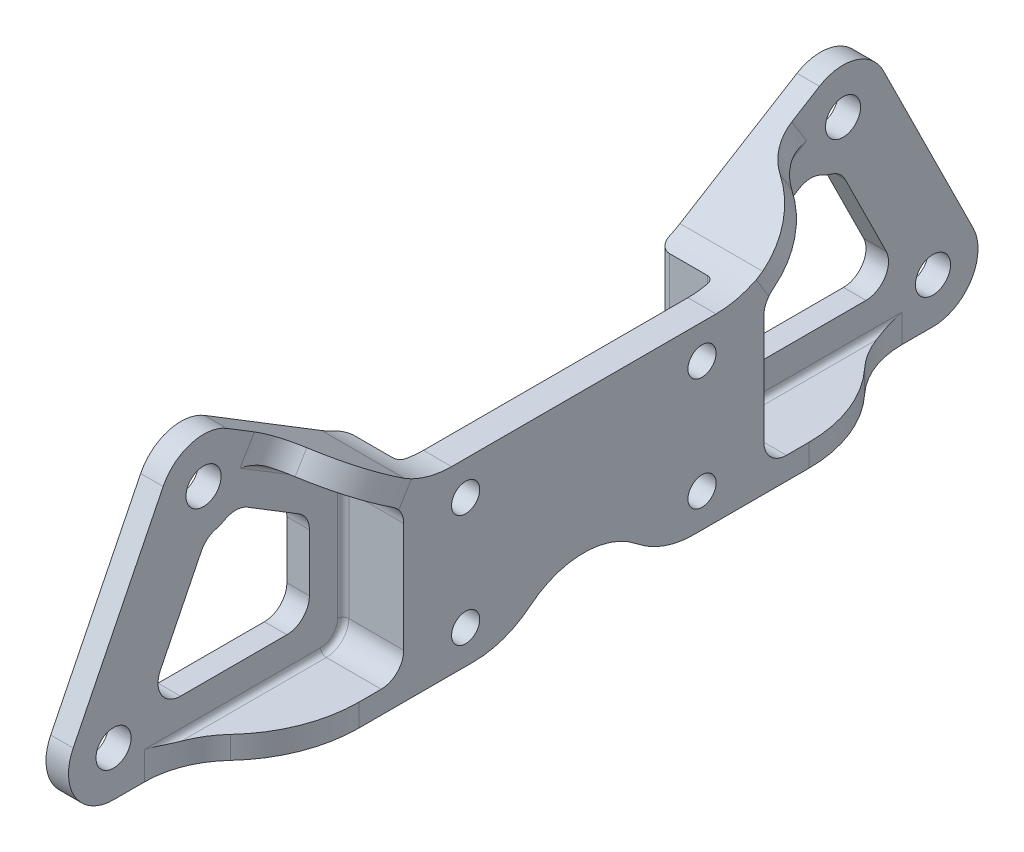
SolidWorks part; units mm, degrees
material "6061-T6 (SS)"
ref_plane "Front Plane" through (0, 0, 0) normal (0, 0, 1) x (1, 0, 0)
ref_plane "Top Plane" through (0, 0, 0) normal (0, 1, 0) x (1, 0, 0)
ref_plane "Right Plane" through (0, 0, 0) normal (1, 0, 0) x (0, 0, -1)
sketch "UprightGeometry" plane through (0, 0, 0) normal (1, 0, 0) x (0, 0, -1)
  line L0 (0, 85.725) -> (0, 0) construction
  line L1 (-44.45, -31.75) -> (44.45, -31.75)
  line L2 (-44.45, -31.75) -> (-44.45, 132.0361)
  line L3 (-44.45, 132.0361) -> (44.45, 132.0361)
  line L4 (44.45, -31.75) -> (44.45, 132.0361)
  line L5 (-22.225, 107.95) -> (22.225, 107.95)
  line L6 (-22.225, 107.95) -> (-22.225, 63.5)
  line L7 (-22.225, 63.5) -> (22.225, 63.5)
  line L8 (22.225, 107.95) -> (22.225, 63.5)
  line L9 (-22.225, 107.95) -> (22.225, 63.5) construction
  line L10 (-22.225, 63.5) -> (22.225, 107.95) construction
  line L11 (-44.45, 38.1) -> (44.45, 38.1) construction
  line L12 (-84.8616, 85.725) -> (88.724, 85.725) construction
  line L13 (88.724, 79.375) -> (-84.8616, 79.375) construction
  line L14 (88.724, 74.7268) -> (-142.7243, 74.7268) construction
  circle A0 centre (0, 0) radius 12.7
  circle A1 centre (0, 0) radius 19.05
  circle A2 centre (-33.3375, 53.975) radius 3.9688
  circle A3 centre (33.3375, 53.975) radius 3.9687
  circle A4 centre (33.3375, 22.225) radius 3.9687
  circle A5 centre (-33.3375, 22.225) radius 3.9688
  point P8 (0, 85.725)
  dimension "D6" = 25.4
  dimension "D7" = 38.1
  dimension "D9" = 7.9375
  dimension "D1" = 85.725
  dimension "D2" = 44.45
  dimension "D3" = 44.45
  dimension "D4" = 88.9
  dimension "D5" = 31.75
  dimension "D8" = 47.625
  dimension "D10" = 66.675
  dimension "D11" = 31.75
  dimension "D12" = 6.35
  dimension "D13" = 10.9982
sketch "CaliperGeometry" plane through (0, 0, 0) normal (1, 0, 0) x (0, 0, -1)
  line L0 (0, 0) -> (0, 136.5858) construction
  line L1 (0, 0) -> (-119.102, 59.0447) construction
  line L2 (-90.1858, 76.6033) -> (-115.5698, 25.4) construction
  line L3 (0, 0) -> (119.102, 59.0447) construction
  line L4 (90.1858, 76.6033) -> (115.5698, 25.4) construction
  line L5 (-44.45, 12.7) -> (-150.9464, 12.7) construction
  line L7 (-44.45, -31.75) -> (-44.45, 132.0361) construction
  line L8 (-22.225, 63.5) -> (22.225, 63.5) construction
  line L9 (-44.45, 63.5) -> (-66.5242, 77.0108) construction
  circle A0 centre (0, 0) radius 110 construction
  circle A1 centre (-115.5698, 25.4) radius 4.953
  circle A2 centre (-90.1858, 76.6033) radius 4.953
  circle A3 centre (115.5698, 25.4) radius 4.953
  circle A4 centre (90.1858, 76.6033) radius 4.953
  circle A5 centre (-115.5698, 25.4) radius 12.7 construction
  circle A6 centre (-90.1858, 76.6033) radius 12.7 construction
  point P7 (-102.8778, 51.0016)
  point P10 (-98.554, 48.8581)
  dimension "D1" = 220
  dimension "D3" = 9.906
  dimension "D7" = 25.4
  dimension "D2" = 57.15
  dimension "D4" = 4.826
  dimension "D5" = 63.63
  dimension "D6" = 50.8
sketch "Sketch3" plane through (0, 0, 0) normal (1, 0, 0) x (0, 0, -1)
  line L0 (-44.45, 63.5) -> (44.45, 63.5)
  line L1 (-44.45, -31.75) -> (-44.45, 132.0361) construction
  line L2 (0, 85.725) -> (0, 0) construction
  line L3 (-44.45, 12.7) -> (44.45, 12.7)
  line L4 (-44.45, 12.7) -> (-115.5698, 12.7)
  line L5 (-44.45, 63.5) -> (-83.5559, 87.4353)
  line L6 (-126.9483, 31.0409) -> (-101.5643, 82.2442)
  line L7 (126.9483, 31.0409) -> (101.5643, 82.2442)
  line L8 (44.45, 63.5) -> (83.5559, 87.4353)
  line L9 (0, 0) -> (-119.102, 59.0447) construction
  line L10 (-22.225, 63.5) -> (22.225, 63.5) construction
  line L11 (0, 0) -> (0, 85.725) construction
  line L12 (44.45, 12.7) -> (115.5698, 12.7)
  circle A0 centre (-90.1858, 76.6033) radius 4.953 construction
  circle A1 centre (-115.5698, 25.4) radius 4.953 construction
  circle A4 centre (33.3375, 53.975) radius 3.9688 construction
  circle A5 centre (-33.3375, 53.975) radius 3.9688 construction
  circle A6 centre (-33.3375, 22.225) radius 3.9688 construction
  circle A7 centre (33.3375, 22.225) radius 3.9688 construction
  circle A8 centre (-90.1858, 76.6033) radius 4.953
  circle A9 centre (-115.5698, 25.4) radius 4.953
  arc A10 (83.5559, 87.4353) -> (101.5643, 82.2442) centre (90.1858, 76.6033) cw
  arc A11 (115.5698, 12.7) -> (126.9483, 31.0409) centre (115.5698, 25.4) ccw
  circle A12 centre (33.3375, 53.975) radius 3.9688
  circle A13 centre (-33.3375, 53.975) radius 3.9688
  circle A14 centre (-33.3375, 22.225) radius 3.9688
  circle A15 centre (33.3375, 22.225) radius 3.9687
  arc A16 (-115.5698, 12.7) -> (-126.9483, 31.0409) centre (-115.5698, 25.4) cw
  arc A17 (-83.5559, 87.4353) -> (-101.5643, 82.2442) centre (-90.1858, 76.6033) ccw
  circle A18 centre (115.5698, 25.4) radius 4.953
  circle A19 centre (90.1858, 76.6033) radius 4.953
  point P7 (0, 63.5)
  point P17 (-114.2563, 56.6425)
  point P29 (0, 12.7)
  point P34 (114.2563, 56.6425)
  dimension "D2" = 12.7
extrude "Boss-Extrude1" add sketch "Sketch3" along normal blind 7.9375
sketch "SpindleGeometry" plane through (0, 0, 0) normal (0, 0, 1) x (1, 0, 0)
  line L0 (0, -31.8425) -> (-38.1, -31.8425)
  line L1 (0, -31.75) -> (0, 132.0361) construction
  line L2 (0, -110) -> (0, 110) construction
  line L3 (-38.1, -31.8425) -> (-38.1, 132.0361)
  line L4 (-38.1, 132.0361) -> (0, 132.0361)
  line L5 (0, 0) -> (116.0127, 0) construction
  line L6 (0, 0) -> (0, 136.5858) construction
  line L7 (27.9, -110) -> (22.9, -110)
  line L8 (27.9, -110) -> (27.9, 110)
  line L9 (27.9, 110) -> (22.9, 110)
  line L10 (22.9, -110) -> (22.9, 110)
  line L11 (25.4, 0) -> (25.4, -129.8502) construction
  line L12 (0, -31.8425) -> (0, 132.0361) construction
  line L13 (-9.144, 104.2064) -> (-9.144, -104.3427) construction
  line L14 (-15.494, 104.2064) -> (-15.494, -104.3427) construction
  line L15 (9.525, 80.2257) -> (9.525, 91.2243)
  line L16 (9.525, 91.2243) -> (0, 96.7235)
  line L17 (0, 96.7235) -> (-9.525, 91.2243)
  line L18 (-9.525, 91.2243) -> (-9.525, 80.2257)
  line L19 (-9.525, 80.2257) -> (0, 74.7265)
  line L20 (0, 74.7265) -> (9.525, 80.2257)
  circle A0 centre (0, 85.725) radius 10.9985 construction
  point P11 (25.4, 0)
  point P16 (0, 110)
  dimension "D1" = 38.1
  dimension "D2" = 5
  dimension "D3" = 25.4
  dimension "D4" = 34.544
  dimension "D5" = 9.144
  dimension "D6" = 19.05
  dimension "D8" = 6.35
sketch "Sketch5" plane through (0, 0, 0) normal (1, 0, 0) x (0, 0, -1)
  line L0 (-44.45, 63.5) -> (-83.5559, 87.4353) construction
  line L1 (-101.5643, 82.2442) -> (-126.9483, 31.0409) construction
  line L3 (126.9483, 31.0409) -> (101.5643, 82.2442) construction
  line L4 (83.5559, 87.4353) -> (44.45, 63.5) construction
  line L5 (-115.5698, 12.7) -> (115.5698, 12.7) construction
  line L6 (-44.45, 63.5) -> (-83.5559, 87.4353)
  line L7 (-101.5643, 82.2442) -> (-126.9483, 31.0409)
  line L8 (-115.5698, 12.7) -> (-44.45, 12.7)
  line L9 (126.9483, 31.0409) -> (101.5643, 82.2442)
  line L10 (83.5559, 87.4353) -> (44.45, 63.5)
  line L11 (44.45, 12.7) -> (115.5698, 12.7)
  line L12 (-44.45, -31.75) -> (-44.45, 132.0361) construction
  line L13 (44.45, -31.75) -> (44.45, 132.0361) construction
  line L14 (-44.45, 12.7) -> (-44.45, 63.5)
  line L15 (44.45, 12.7) -> (44.45, 63.5)
  arc A0 (-83.5559, 87.4353) -> (-101.5643, 82.2442) centre (-90.1858, 76.6033) ccw construction
  arc A1 (-126.9483, 31.0409) -> (-115.5698, 12.7) centre (-115.5698, 25.4) ccw construction
  arc A2 (115.5698, 12.7) -> (126.9483, 31.0409) centre (115.5698, 25.4) ccw construction
  arc A3 (101.5643, 82.2442) -> (83.5559, 87.4353) centre (90.1858, 76.6033) ccw construction
  arc A4 (-83.5559, 87.4353) -> (-101.5643, 82.2442) centre (-90.1858, 76.6033) ccw
  arc A5 (-126.9483, 31.0409) -> (-115.5698, 12.7) centre (-115.5698, 25.4) ccw
  arc A6 (115.5698, 12.7) -> (126.9483, 31.0409) centre (115.5698, 25.4) ccw
  arc A7 (101.5643, 82.2442) -> (83.5559, 87.4353) centre (90.1858, 76.6033) ccw
  circle A8 centre (-90.1858, 76.6033) radius 4.953 construction
  circle A9 centre (-115.5698, 25.4) radius 4.953 construction
  circle A10 centre (115.5698, 25.4) radius 4.953 construction
  circle A11 centre (90.1858, 76.6033) radius 4.953 construction
  circle A12 centre (-90.1858, 76.6033) radius 4.953
  circle A13 centre (-115.5698, 25.4) radius 4.953
  circle A14 centre (115.5698, 25.4) radius 4.953
  circle A15 centre (90.1858, 76.6033) radius 4.953
extrude "Boss-Extrude2" add sketch "Sketch5" along direction (1, 0, 0) on the side against the normal up to vertex (15.494 mm away) up to point (-15.494, 104.2064, 0)
sketch "Sketch10" plane through (0, 0, 0) normal (1, 0, 0) x (0, 0, -1)
  circle A2 centre (0, 0) radius 23.8125
  circle A3 centre (0, 0) radius 23.8125
  dimension "D1" = 4.7625
extrude "Cut-Extrude3" cut sketch "Sketch10" along normal through all
sketch "Sketch7" plane through (7.9375, 0, 0) normal (-1, 0, 0) x (0, 0, 1)
  line L0 (81.9704, 71.7423) -> (79.9379, 85.2209)
  line L1 (0, 0) -> (119.102, 59.0447) construction
  line L2 (-0.0024, -0.0012) -> (-71.617, -35.5041) construction
  line L3 (106.7271, 21.8044) -> (115.5698, 12.7)
  line L5 (95.5306, 25.4836) -> (90.8737, 24.708)
  line L7 (44.45, 63.5) -> (83.5559, 87.4353) construction
  line L8 (101.5643, 82.2442) -> (126.9483, 31.0409) construction
  line L9 (44.45, 63.5) -> (83.5559, 87.4353) construction
  line L10 (78.1199, 60.6036) -> (74.6832, 57.3667)
  line L12 (101.5643, 82.2442) -> (126.9483, 31.0409)
  line L14 (79.9379, 85.2209) -> (83.5559, 87.4353)
  arc A0 (74.6832, 57.3667) -> (90.8737, 24.708) centre (87.7444, 43.4993) ccw
  arc A1 (106.7271, 21.8044) -> (95.5306, 25.4836) centre (97.6168, 12.9561) ccw
  arc A2 (81.9704, 71.7423) -> (78.1199, 60.6036) centre (69.4124, 69.8486) cw
  arc A3 (115.5698, 12.7) -> (126.9483, 31.0409) centre (115.5698, 25.4) ccw construction
  arc A4 (101.5643, 82.2442) -> (83.5559, 87.4353) centre (90.1858, 76.6033) ccw construction
  arc A5 (115.5698, 12.7) -> (126.9483, 31.0409) centre (115.5698, 25.4) ccw
  arc A6 (101.5643, 82.2442) -> (83.5559, 87.4353) centre (90.1858, 76.6033) ccw
  point P4 (70.6766, 35.0379)
  dimension "D1" = 38.1
  dimension "D3" = 25.4
  dimension "D2" = 35.941
  dimension "D4" = 31.75
  dimension "D5" = 21.844
extrude "Cut-Extrude6" cut sketch "Sketch7" along normal up to vertex (17.0815 mm away) up to point (-9.144, 104.2064, 0)
sketch "Sketch9" plane through (7.9375, 0, 0) normal (1, 0, 0) x (0, 0, -1)
  line L0 (-50.8, 59.9416) -> (-50.8, 19.05)
  line L1 (-50.8, 19.05) -> (-95.25, 19.05)
  line L2 (-50.8, 59.9416) -> (-72.4642, 73.2015)
  line L3 (-72.4642, 73.2015) -> (-61.3726, 91.323)
  line L5 (-44.45, -31.75) -> (-44.45, 132.0361) construction
  line L6 (-77.6624, 19.05) -> (-77.6624, 12.7) construction
  line L7 (-44.45, 63.5) -> (-79.9379, 85.2209) construction
  line L8 (-44.45, 12.7) -> (-150.9464, 12.7) construction
  line L10 (-61.864, 66.7135) -> (-58.5491, 72.1296) construction
  line L12 (-115.5698, 12.7) -> (-256.5396, 12.7) construction
  line L14 (-44.45, 63.5) -> (-66.5242, 77.0108) construction
  line L15 (-61.3726, 91.323) -> (-134.8019, 91.323)
  line L16 (-134.8019, 91.323) -> (-134.8019, 7.8197)
  line L17 (-134.8019, 7.8197) -> (-95.25, 7.8197)
  line L18 (-95.25, 7.8197) -> (-95.25, 19.05)
  dimension "D2" = 6.35
  dimension "D1" = 6.35
  dimension "D3" = 44.45
  dimension "D4" = 25.4
extrude "Cut-Extrude2" cut sketch "Sketch9" against normal up to surface (17.0815 mm away) up to face at (-9.144, 76.6033, 95.1388)
fillet "Fillet4" radius 6.35 2 edges at (-0.6033, 59.9416, 50.8) (-0.6033, 19.05, 50.8)
sketch "Sketch11" plane through (0, 0, 0) normal (1, 0, 0) x (0, 0, -1)
  line L0 (-106.9083, 28.575) -> (-89.3817, 63.9288)
  line L1 (-126.9483, 31.0409) -> (-101.5643, 82.2442) construction
  line L6 (-95.25, 28.575) -> (-60.325, 28.575)
  line L7 (-60.325, 28.575) -> (-60.325, 54.604)
  line L8 (-60.325, 54.604) -> (-77.4366, 65.0774)
  line L9 (-106.9083, 28.575) -> (-60.325, 28.575)
  line L10 (-60.325, 28.575) -> (-60.325, 54.604)
  line L11 (-60.325, 54.604) -> (-81.3552, 67.4758)
  arc A2 (-89.3817, 63.9288) -> (-81.3552, 67.4758) centre (-90.1858, 76.6033) ccw
  arc A5 (-83.5559, 87.4353) -> (-101.5643, 82.2442) centre (-90.1858, 76.6033) ccw construction
  dimension "D2" = 19.05
  dimension "D1" = 9.525
extrude "Cut-Extrude7" cut sketch "Sketch11" against normal through all
fillet "Fillet14" radius 6.35 5 edges at (-12.319, 28.575, 60.325) (-12.319, 54.604, 60.325) (-12.319, 63.9288, 89.3817) (-12.319, 67.4758, 81.3552) (-12.319, 28.575, 106.9083)
mirror "Mirror1" about plane through (0, 0, 0) normal (0, 0, 1) of "Fillet14", "Cut-Extrude7", "Cut-Extrude6", "Fillet4", "Cut-Extrude2"
fillet "Fillet2" radius 1.5875 2 edges at (0, 38.1, -44.45)
fillet "Fillet3" radius 25.4 2 edges at (3.175, 63.5, 44.45) (3.175, 63.5, -44.45)
fillet "Fillet6" radius 25.4 2 edges at (3.9688, 12.7, -20.1431) (3.9688, 12.7, 20.1431)
fillet "Fillet7" radius 38.1 2 edges at (7.9375, 15.875, 95.25) (7.9375, 15.875, -95.25)
fillet "Fillet10" radius 25.4 4 edges at (7.9375, 75.9095, 70.8067) (-9.144, 15.875, 95.25) (-9.144, 15.875, -95.25) (7.9375, 75.9095, -70.8067)
fillet "Fillet12" radius 12.7 2 edges at (-9.144, 75.9095, 70.8067) (-9.144, 75.9095, -70.8067)
fillet "Fillet9" radius 1.5875 10 edges at (-9.144, 19.05, 81.9766) (-9.144, 20.9099, 52.6599) (-9.144, 40.8916, 50.8) (-9.144, 59.4874, 51.6105) (-9.144, 69.5307, 66.4669) (-9.144, 19.05, -81.9766) (-9.144, 20.9099, -52.6599) (-9.144, 69.5307, -66.4669) (-9.144, 59.4874, -51.6105) (-9.144, 40.8916, -50.8)
fillet "Fillet13" radius 3.175 2 edges at (-15.494, 38.6145, -44.45) (-15.494, 38.6145, 44.45)
